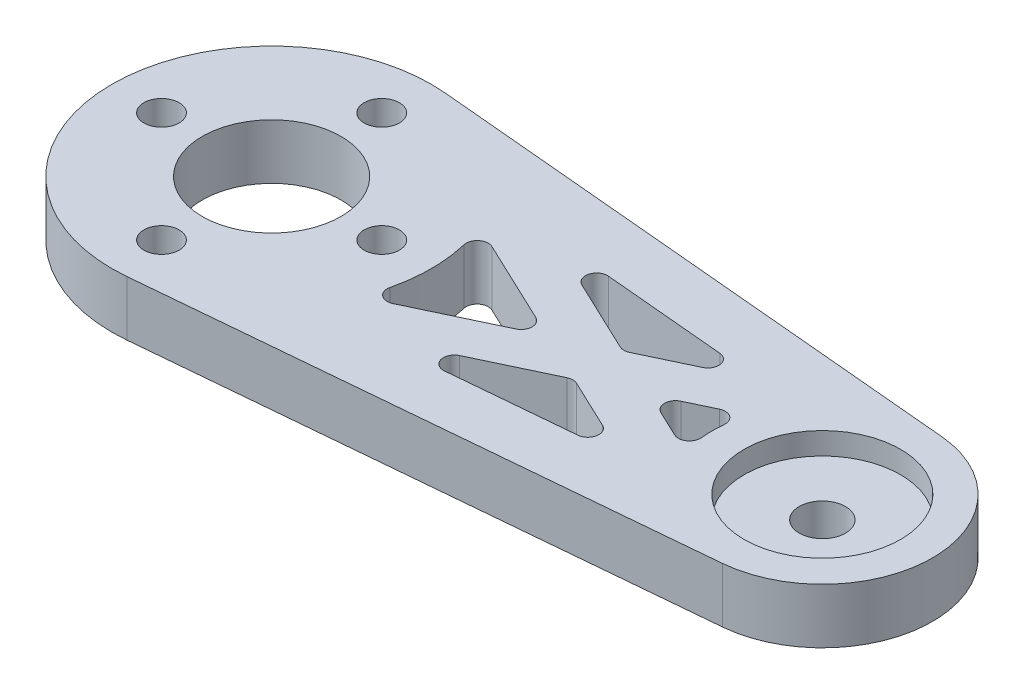
SolidWorks part; units mm, degrees
material "三聚氰胺甲醛树脂"
ref_plane "前视基准面" through (0, 0, 0) normal (0, 0, 1) x (1, 0, 0)
ref_plane "上视基准面" through (0, 0, 0) normal (0, 1, 0) x (1, 0, 0)
ref_plane "右视基准面" through (0, 0, 0) normal (1, 0, 0) x (0, 0, -1)
sketch "草图1" plane through (0, 0, 0) normal (0, 1, 0) x (1, 0, 0)
  line L0 (0, 0) -> (-5.9584, 0) construction
  line L1 (1.305, -14.4412) -> (50.9, -9.9594)
  line L2 (1.305, 14.4412) -> (50.9, 9.9594)
  line L3 (17.5402, 7.9537) -> (37.9007, 6.1138)
  line L4 (17.5402, -7.9537) -> (37.9007, -6.1138)
  line L5 (11.765, 8.4755) -> (41.8249, -5.7591) construction
  line L6 (11.765, -8.4755) -> (41.8249, 5.7591) construction
  line L7 (13.4262, 5.476) -> (24.99, 0)
  line L8 (17.5402, 7.9537) -> (29.6631, 2.2129)
  line L9 (13.4262, -5.476) -> (24.99, 0)
  line L10 (17.5402, -7.9537) -> (29.6631, -2.2129)
  line L11 (29.6631, 2.2129) -> (37.9007, 6.1138)
  line L12 (34.3362, 0) -> (40.4246, -2.8831)
  line L13 (34.3362, 0) -> (40.4246, 2.8831)
  line L14 (29.6631, -2.2129) -> (37.9007, -6.1138)
  circle A0 centre (0, 0) radius 10 construction
  circle A1 centre (-10, 0) radius 1.6
  circle A2 centre (0, 10) radius 1.6
  circle A3 centre (10, 0) radius 1.6
  circle A4 centre (0, -10) radius 1.6
  arc A5 (1.305, 14.4412) -> (1.305, -14.4412) centre (0, 0) ccw
  circle A6 centre (0, 0) radius 6.3
  arc A7 (40.4246, 2.8831) -> (40.4246, -2.8831) centre (50, 0) ccw
  circle A8 centre (50, 0) radius 2.1
  circle A9 centre (50, 0) radius 7.1
  arc A10 (13.4262, -5.476) -> (13.4262, 5.476) centre (0, 0) ccw
  circle A11 centre (0, 0) radius 14.5 construction
  arc A12 (50.9, -9.9594) -> (50.9, 9.9594) centre (50, 0) ccw
  circle A13 centre (50, 0) radius 10 construction
  point P15 (0, 0)
  dimension "D1" = 20
  dimension "D2" = 3.2
  dimension "D4" = 20
  dimension "D5" = 29
  dimension "D6" = 12.6
  dimension "D7" = 4.2
  dimension "D8" = 14.2
  dimension "D3" = 50
  dimension "D9" = 5
  dimension "D10" = 5
  dimension "D11" = 2
  dimension "D12" = 2
  dimension "D13" = 2
  dimension "D14" = 2
extrude "凸台-拉伸1" add sketch "草图1" along normal blind 5 contours L1 A7 L2 A5 A9 A1 A2 A3 A4 A6 region at (-13.7005, 0, 0)
extrude "凸台-拉伸2" add sketch "草图1<3>" along normal blind 3 contours A9 A8 region at (43.1008, 0, 0)
sketch "草图1<3>" plane through (0, 0, 0) normal (0, 1, 0) x (1, 0, 0) same geometry as "草图1"
fillet "圆角1" radius 1 3 edges at (34.3362, 2.5, 0) (40.4246, 2.5, -2.8831) (40.4246, 2.5, 2.8831)
fillet "圆角2" radius 1 3 edges at (29.6631, 2.5, 2.2129) (17.5402, 2.5, 7.9537) (37.9007, 2.5, 6.1138)
fillet "圆角3" radius 1 3 edges at (17.5402, 2.5, -7.9537) (29.6631, 2.5, -2.2129) (37.9007, 2.5, -6.1138)
fillet "圆角4" radius 1 3 edges at (13.4262, 2.5, -5.476) (24.99, 2.5, 0) (13.4262, 2.5, 5.476)
sketch "草图2" plane through (0, 0, 0) normal (0, 1, 0) x (1, 0, 0)
  circle A0 centre (0, -10) radius 3
  circle A1 centre (-10, 0) radius 3
  circle A2 centre (0, 10) radius 3
  circle A3 centre (10, 0) radius 3
  dimension "D1" = 6
  dimension "D2" = 4
extrude "切除-拉伸1" cut sketch "草图2" along normal blind 1
